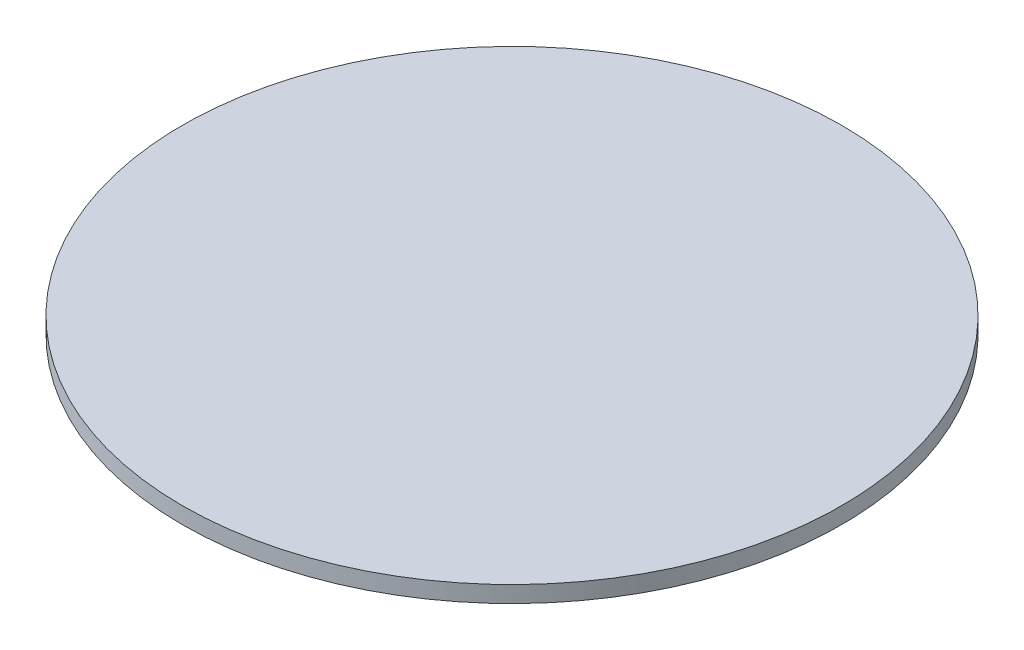
SolidWorks part; units mm, degrees
material "Maple"
ref_plane "Wasteboard" through (0, 0, 0) normal (0, 0, 1) x (1, 0, 0)
ref_plane "Left-Right" through (0, 0, 0) normal (0, 1, 0) x (1, 0, 0)
ref_plane "Front-Back" through (0, 0, 0) normal (1, 0, 0) x (0, 0, -1)
sketch "Sketch1" plane through (0, 0, 0) normal (0, 0, 1) x (1, 0, 0)
  line L0 (0, 42.3235) -> (0, -39.784) construction
  line L1 (0, -55) -> (0, 55) construction
  line L2 (0, 3.1923) -> (41.2814, 3.1923) construction
  line L3 (41.2814, 3.1923) -> (41.2814, 18.1923) construction
  line L4 (31.7163, 3.1923) -> (31.7163, 10.1923) construction
  line L5 (0, 30.7268) -> (2.5, 30.7268) construction
  line L6 (0, 37.5678) -> (4, 37.5678) construction
  line L7 (0, 43.5419) -> (6.5, 43.5419) construction
  line L8 (4, -2.2844) -> (4, 8.669)
  line L9 (4, 8.669) -> (6.5, 8.669)
  line L10 (6.5, 8.669) -> (6.5, 14.669)
  line L11 (6.5, 14.669) -> (8.9483, 14.669)
  line L12 (8.9483, 14.669) -> (10, 10.6923)
  line L13 (10, 10.6923) -> (8.5, 3.1923)
  line L14 (10, -4.3077) -> (8.5, 3.1923)
  line L15 (8.9483, -8.2844) -> (10, -4.3077)
  line L16 (6.5, -8.2844) -> (8.9483, -8.2844)
  line L17 (6.5, -2.2844) -> (6.5, -8.2844)
  line L18 (4, -2.2844) -> (6.5, -2.2844)
  line L19 (29.4361, 3.1923) -> (29.4361, 14.6923) construction
  line L20 (29.4361, 14.6923) -> (-15.0373, 14.6923) construction
  line L21 (10, 10.6923) -> (8.0155, 18.1962) construction
  line L22 (10, 10.6923) -> (4.6827, 10.6923)
  point P25 (4, 3.1923)
  dimension "D1" = 15
  dimension "D2" = 7
  dimension "D3" = 4
  dimension "D4" = 2.5
  dimension "D5" = 6.5
  dimension "D6" = 6
  dimension "D7" = 7.5
  dimension "D8" = 10
  dimension "D9" = 2.5
  dimension "D10" = 82.1075
  dimension "D11" = 6
  dimension "D12" = 8.5
  dimension "D13" = 11.5
  dimension "D14" = 4.5
  dimension "D15" = 75.187
  dimension "D16" = 78.69
revolve "Revolve1" add sketch "Sketch1" angle 360 about L0 rebuild error yes
sketch "Sketch2" plane through (0, -2.2844, 0) normal (0, -1, 0) x (1, 0, 0)
  circle A0 centre (0, 0) radius 4
extrude "Boss-Extrude1" add sketch "Sketch2" against normal blind 0.2
